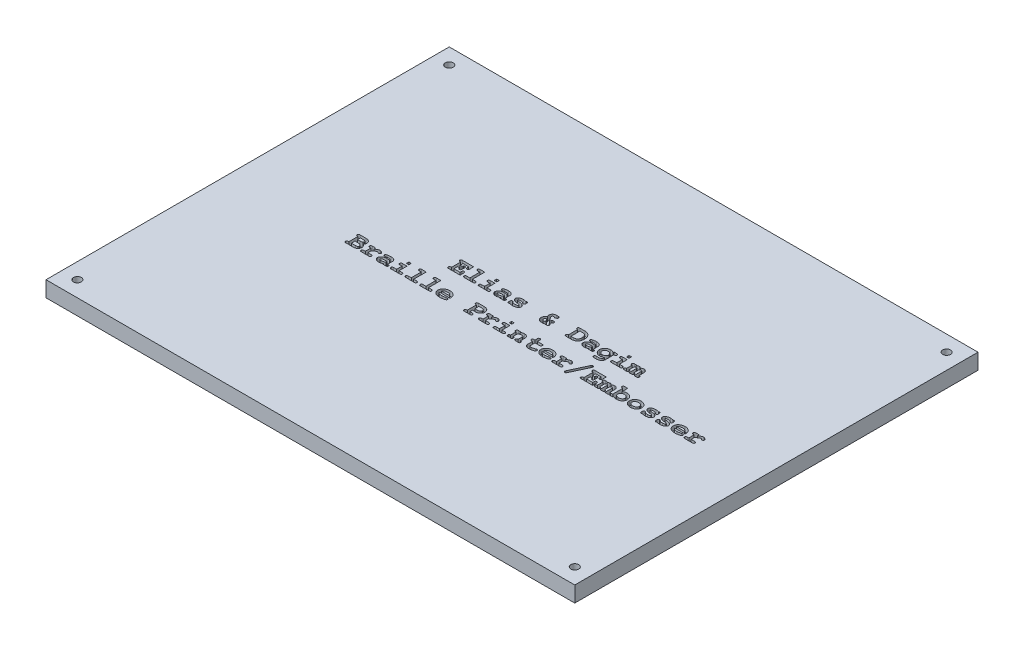
SolidWorks part; units mm, degrees
ref_plane "Front Plane" through (0, 0, 0) normal (0, 0, 1) x (1, 0, 0)
ref_plane "Top Plane" through (0, 0, 0) normal (0, 1, 0) x (1, 0, 0)
ref_plane "Right Plane" through (0, 0, 0) normal (1, 0, 0) x (0, 0, -1)
sketch "Sketch2" plane through (0, 0, 0) normal (0, 1, 0) x (1, 0, 0)
  line L0 (-168.2601, 118.5) -> (168.7399, 118.5) construction
  line L1 (168.7399, 128.5) -> (-168.2601, 128.5)
  line L2 (168.7399, 128.5) -> (168.7399, -128.5)
  line L3 (168.7399, -128.5) -> (-168.2601, -128.5)
  line L4 (-168.2601, 128.5) -> (-168.2601, -128.5)
  line L5 (-158.2601, 128.5) -> (-158.2601, -128.5) construction
  line L6 (158.7399, 128.5) -> (158.7399, -128.5) construction
  line L7 (168.7399, -118.5) -> (-168.2601, -118.5) construction
  point P0 (0, 0)
  dimension "D1" = 257
  dimension "D2" = 337
  dimension "D3" = 10
  dimension "D4" = 10
  dimension "10" = 10
  dimension "D5" = 10
extrude "Boss-Extrude1" add sketch "Sketch2" along normal blind 10
sketch "Sketch3" plane through (0, 10, 0) normal (0, 1, 0) x (1, 0, 0)
  line L0 (-158.2601, -128.5) -> (-158.2601, 128.5) construction
  line L1 (-168.2601, -128.5) -> (168.7399, -128.5) construction
  line L2 (168.7399, 128.5) -> (-168.2601, 128.5) construction
  line L3 (-168.2601, -118.5) -> (168.7399, -118.5) construction
  line L4 (-168.2601, 128.5) -> (-168.2601, -128.5) construction
  line L5 (168.7399, -128.5) -> (168.7399, 128.5) construction
  line L6 (158.7399, 128.5) -> (158.7399, -128.5) construction
  line L7 (-168.2601, 118.5) -> (168.7399, 118.5) construction
  circle A0 centre (-158.2601, 118.5) radius 2.5
  circle A1 centre (-158.2601, -118.5) radius 2.5
  circle A2 centre (158.7399, -118.5) radius 2.5
  circle A3 centre (158.7399, 118.5) radius 2.5
  dimension "D5" = 5
  dimension "D6" = 5
  dimension "D7" = 5
  dimension "D8" = 5
  dimension "D1" = 10
  dimension "D2" = 10
  dimension "D3" = 10
  dimension "D4" = 10
extrude "Cut-Extrude1" cut sketch "Sketch3" against normal blind 10
sketch "Sketch7" plane through (0, 10, 0) normal (0, 1, 0) x (1, 0, 0)
  text T0 "     Elias & Dagim\r\nBraille Printer/Embosser " font "Courier New" height in points 40
extrude "Cut-Extrude2" cut sketch "Sketch7" against normal blind 3
